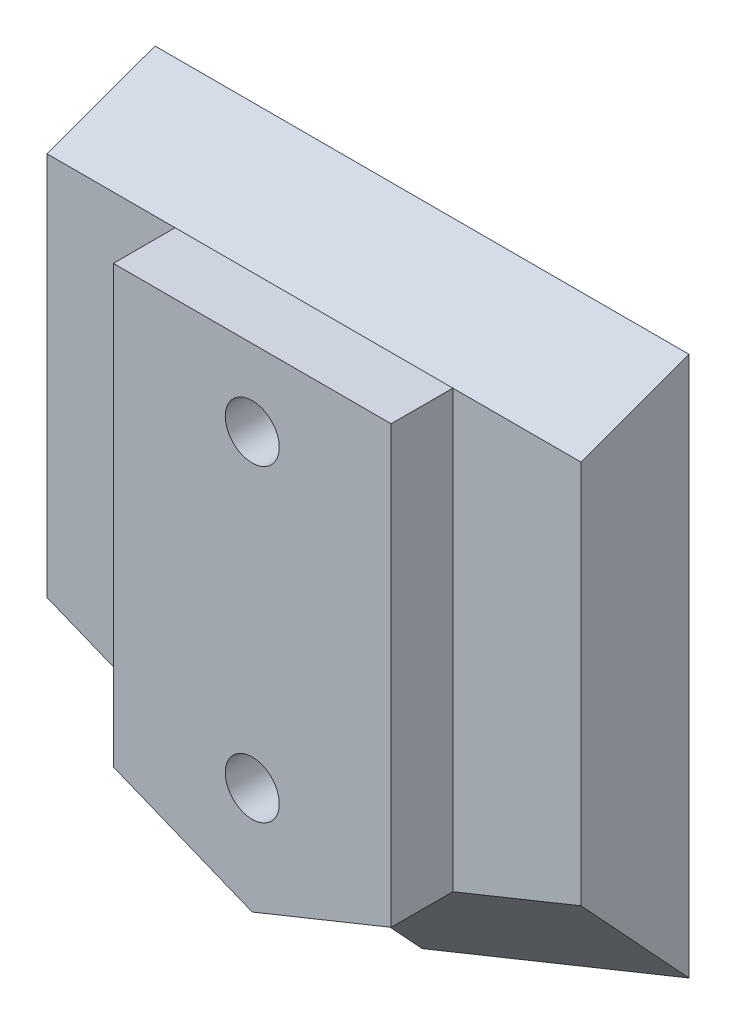
SolidWorks part; units mm, degrees
ref_plane "Plano frontal" through (0, 0, 0) normal (0, 0, 1) x (1, 0, 0)
ref_plane "Plano superior" through (0, 0, 0) normal (0, 1, 0) x (1, 0, 0)
ref_plane "Plano direito" through (0, 0, 0) normal (1, 0, 0) x (0, 0, -1)
sketch "Esboço1" plane through (0, 0, 0) normal (0, 0, 1) x (1, 0, 0)
  line L1 (-17.3, 13) -> (17.3, 13)
  line L2 (-17.3, 13) -> (-17.3, -13)
  line L3 (-17.3, -13) -> (17.3, -13)
  line L4 (17.3, 13) -> (17.3, -13)
  line L5 (-17.3, 13) -> (17.3, -13) construction
  line L6 (-17.3, -13) -> (17.3, 13) construction
  point P0 (0, 0)
  dimension "D1" = 34.6
  dimension "D2" = 26
extrude "Ressalto-extrusão1" add sketch "Esboço1" along normal blind 7
sketch "Esboço10" plane through (0, 0, 0) normal (0, 0, -1) x (-1, 0, 0)
  line L0 (-17.3, -19.5) -> (0, -26.5)
  line L1 (-17.3, 13) -> (17.3, 13)
  line L2 (-17.3, 13) -> (-17.3, 15.5)
  line L3 (-17.3, 15.5) -> (17.3, 15.5)
  line L4 (17.3, 13) -> (17.3, 15.5)
  line L5 (0, -26.5) -> (17.3, -19.5)
  line L6 (-17.3, -19.5) -> (-17.3, -13)
  line L7 (-17.3, -13) -> (17.3, -13)
  line L8 (17.3, -13) -> (17.3, -19.5)
  dimension "D1" = 7
  dimension "D2" = 35
  dimension "D3" = 2.5
extrude "Ressalto-extrusão4" add sketch "Esboço10" against normal up to surface (7 mm away) up to face at (0, 0, 7)
chamfer "Chanfro1" distance 7 angle 45 2 edges at (8.65, -23, 7) (-8.65, -23, 7)
chamfer "Chanfro2" distance 7 angle 20 1 edges at (0, 15.5, 7) first distance on face at (0, 15.5, 3.5)
sketch "Esboço13" plane through (0, 0, 7) normal (0, 0, 1) x (1, 0, 0)
  line L0 (0, 0) -> (0, 9.275) construction
  line L5 (17.3, -11.9487) -> (17.3, 12.9522)
  line L6 (17.3, 12.9522) -> (-17.3, 12.9522)
  line L7 (-17.3, 12.9522) -> (-17.3, -11.9487)
  line L8 (-17.3, -11.9487) -> (0, -18.9487)
  line L9 (0, -18.9487) -> (17.3, -11.9487)
  line L10 (9, -15.3071) -> (9, 12.9522)
  line L11 (9, 12.9522) -> (-9, 12.9522)
  line L12 (-9, 12.9522) -> (-9, -15.3071)
  line L13 (-9, -15.3071) -> (0, -18.9487)
  line L14 (0, -18.9487) -> (9, -15.3071)
  dimension "D2" = 18
  dimension "D1" = 0
extrude "Ressalto-extrusão5" add sketch "Esboço13" along normal blind 4
sketch "Esboço11" plane through (0, 0, 11) normal (0, 0, 1) x (1, 0, 0)
  line L0 (0, 9.9803) -> (0, 0) construction
  circle A2 centre (0, -12) radius 1.75
  circle A3 centre (0, 8) radius 1.75
  dimension "D1" = 20
  dimension "D2" = 3.5
  dimension "D3" = 8
extrude "Corte-extrusão1" cut sketch "Esboço11" against normal through all
sketch "Esboço12" plane through (0, 0, 0) normal (0, 0, -1) x (-1, 0, 0)
  circle A1 centre (0, 8) radius 3.5
  circle A3 centre (0, -12) radius 3.5
  dimension "D1" = 7
extrude "Corte-extrusão2" cut sketch "Esboço12" against normal blind 3
